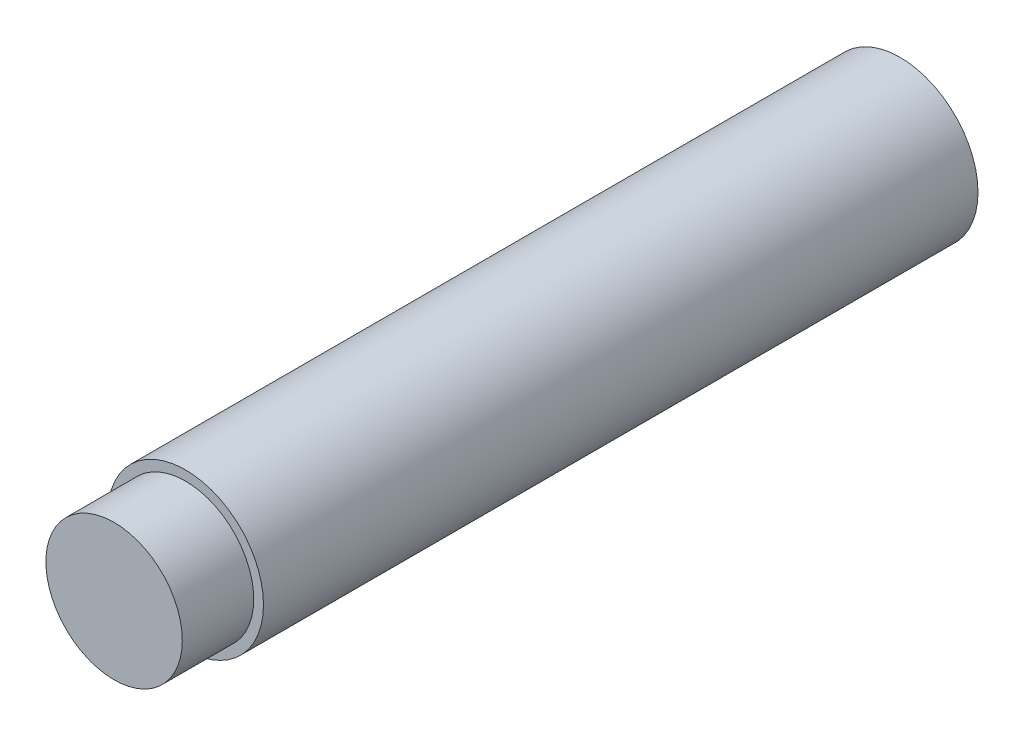
SolidWorks part; units mm, degrees
ref_plane "Front" through (0, 0, 0) normal (0, 0, 1) x (1, 0, 0)
ref_plane "Top" through (0, 0, 0) normal (0, 1, 0) x (1, 0, 0)
ref_plane "Right" through (0, 0, 0) normal (1, 0, 0) x (0, 0, -1)
other "Configuration Table"
sketch "Эскиз1" plane through (0, 0, 0) normal (0, 0, 1) x (1, 0, 0)
  circle A0 centre (0, 0) radius 6
extrude "Бобышка-Вытянуть1" add sketch "Эскиз1" along normal blind 55
sketch "Эскиз2" plane through (0, 0, 55) normal (0, 0, 1) x (1, 0, 0)
  circle A0 centre (0, 0) radius 5.25
extrude "Бобышка-Вытянуть2" add sketch "Эскиз2" along normal blind 5.5
